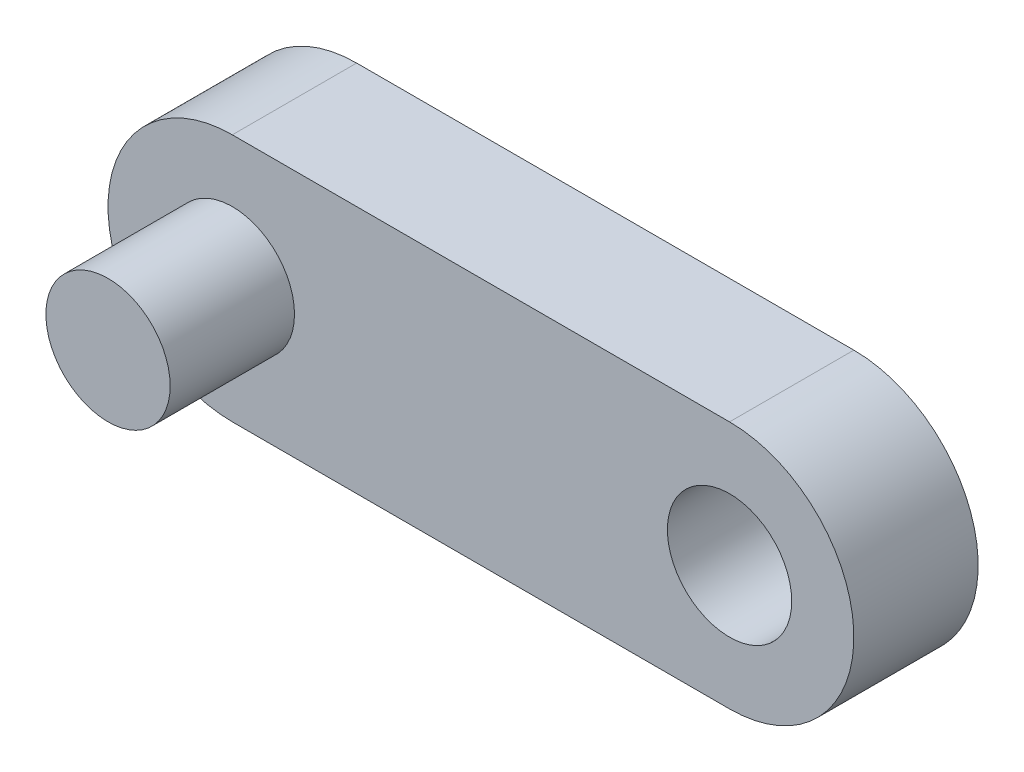
SolidWorks part; units mm, degrees
ref_plane "Front Plane" through (0, 0, 0) normal (0, 0, 1) x (1, 0, 0)
ref_plane "Top Plane" through (0, 0, 0) normal (0, 1, 0) x (1, 0, 0)
ref_plane "Right Plane" through (0, 0, 0) normal (1, 0, 0) x (0, 0, -1)
sketch "Sketch1" plane through (0, 0, 0) normal (0, 0, 1) x (1, 0, 0)
  line L0 (-10, 0) -> (10, 0) construction
  line L1 (-10, 5) -> (10, 5)
  line L2 (-10, -5) -> (10, -5)
  arc A0 (-10, 5) -> (-10, -5) centre (-10, 0) ccw
  arc A1 (10, -5) -> (10, 5) centre (10, 0) ccw
  circle A2 centre (-10, 0) radius 2.5
  circle A3 centre (10, 0) radius 2.5
  point P2 (0, 0)
  dimension "D1" = 5
  dimension "D2" = 5
  dimension "D3" = 20
extrude "Boss-Extrude1" add sketch "Sketch1" along normal blind 5
extrude "Boss-Extrude2" add sketch "Sketch1<2>" along normal blind 10 contours A2 region at (-10, 0, 0)
sketch "Sketch1<2>" plane through (0, 0, 0) normal (0, 0, 1) x (1, 0, 0) same geometry as "Sketch1"
